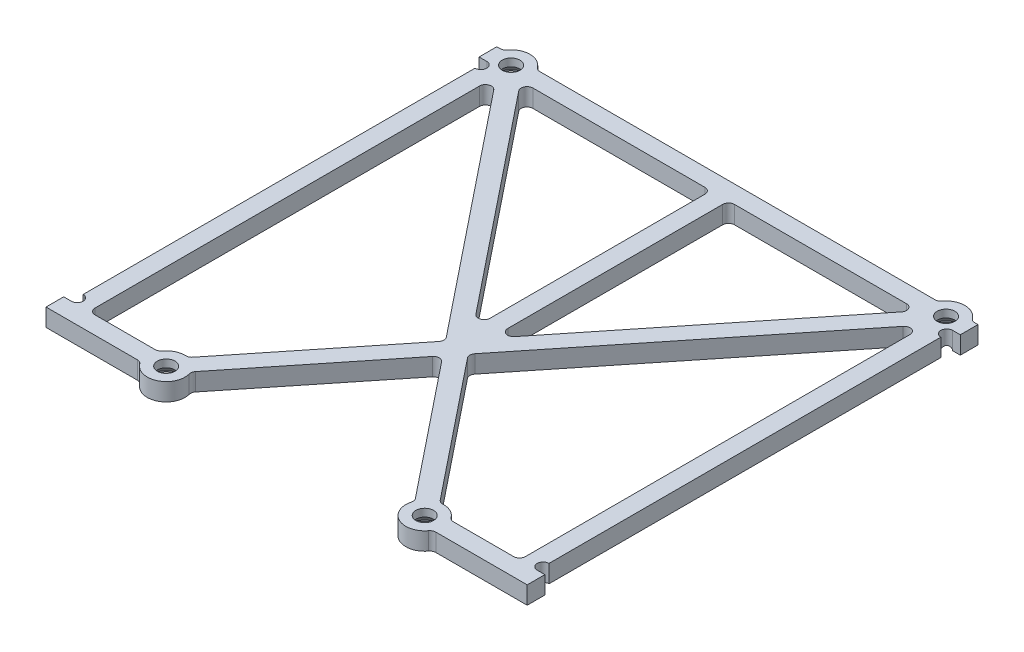
SolidWorks part; units mm, degrees
ref_plane "Front Plane" through (0, 0, 0) normal (0, 0, 1) x (1, 0, 0)
ref_plane "Top Plane" through (0, 0, 0) normal (0, 1, 0) x (1, 0, 0)
ref_plane "Right Plane" through (0, 0, 0) normal (1, 0, 0) x (0, 0, -1)
sketch "Sketch1" plane through (0, 0, 0) normal (0, 1, 0) x (1, 0, 0)
  line L0 (-36.88, 36.725) -> (36.88, 36.725) construction
  line L1 (-39.5, -35.225) -> (-39.5, 35.225)
  line L2 (21.92, -36.725) -> (-21.92, -36.725) construction
  line L3 (-36.5, -35.225) -> (-36.5, 35.225)
  line L4 (0, -40.095) -> (0, -36.725) construction
  line L5 (0, 36.725) -> (0, -36.725) construction
  line L6 (40.8, 38.225) -> (-40.8, 38.225)
  line L9 (40.8, 38.225) -> (40.8, 35.225)
  line L17 (40.8, 35.225) -> (-40.8, 35.225)
  line L18 (-40.8, 38.225) -> (-40.8, 35.225)
  line L23 (40.8, 38.225) -> (-40.8, 35.225) construction
  line L24 (40.8, 35.225) -> (-40.8, 38.225) construction
  line L34 (-40.8, -35.225) -> (40.8, -35.225)
  line L35 (-40.8, -35.225) -> (-40.8, -38.225)
  line L48 (-40.8, -38.225) -> (40.8, -38.225)
  line L54 (40.8, -35.225) -> (40.8, -38.225)
  line L55 (-40.8, -35.225) -> (40.8, -38.225) construction
  line L56 (-40.8, -38.225) -> (40.8, -35.225) construction
  line L60 (-21.92, -36.725) -> (36.88, 36.725) construction
  line L62 (21.92, -36.725) -> (-36.88, 36.725) construction
  line L64 (-1.5, 36.725) -> (-1.5, -36.725)
  line L65 (1.5, 36.725) -> (1.5, -36.725)
  line L66 (23.091, -35.7876) -> (-35.709, 37.6624)
  line L67 (20.749, -37.6624) -> (-38.051, 35.7876)
  line L68 (-20.749, -37.6624) -> (38.051, 35.7876)
  line L69 (-23.091, -35.7876) -> (35.709, 37.6624)
  line L71 (-36.5, 0) -> (-39.5, 0) construction
  line L73 (36.5, -35.225) -> (36.5, 35.225)
  line L74 (39.5, -35.225) -> (39.5, 35.225)
  circle A0 centre (21.92, -36.725) radius 1.5
  circle A1 centre (-21.92, -36.725) radius 1.5
  circle A2 centre (-36.88, 36.725) radius 1.5
  circle A3 centre (36.88, 36.725) radius 1.5
  circle A4 centre (-36.88, 36.725) radius 3.2
  circle A5 centre (-21.92, -36.725) radius 3.2
  circle A6 centre (21.92, -36.725) radius 3.2
  circle A7 centre (36.88, 36.725) radius 3.2
  circle A8 centre (0, -40.095) radius 16
  circle A9 centre (-39.5, 34.225) radius 1
  circle A10 centre (39.5, 34.225) radius 1
  circle A11 centre (-39.5, -34.225) radius 1
  circle A12 centre (39.5, -34.225) radius 1
  circle A13 centre (-35.5, 31.0009) radius 1
  circle A14 centre (35.5, 31.0009) radius 1
  point P10 (0, 0)
  point P58 (-35.2083, 29.9906)
  dimension "D4" = 3
  dimension "D5" = 6.4
  dimension "D6" = 32
  dimension "D11" = 1.5
  dimension "D9" = 3
  dimension "D17" = 2
  dimension "D1" = 74.958
  dimension "D2" = 43.84
  dimension "D3" = 73.76
  dimension "D7" = 3.37
  dimension "D8" = 81.6
  dimension "D10" = 79
  dimension "D12" = 1.5
  dimension "D13" = 1.5
  dimension "D14" = 1.5
  dimension "D15" = 1.5
  dimension "D16" = 1.5
extrude "Shape" add sketch "Sketch1" along normal blind 3 contours L9 | L9 | A4 L1 L34 L3 | A5 L34 L35 L48 | L34 A5 L48 A1 L69 | L69 A5 L34 | L48 A5 | L48 A5 L68 A1 | L68 A5 L34 A1 | L34 A5 L69 | A5 L68 L34 | A5 L34 L68 L64 L67 L69 | L64 L68 L67 | L69 L64 L67 L68 L65 L66 | L69 L67 L64 | L65 L68 L66 | A4 L67 L69 L64 L66 L17 | L64 L69 L66 | L69 L66 L65 | L68 L67 L65 | L66 L69 L65 L17 L64 | A6 L66 L68 L65 L67 L34 | A7 L17 L69 L65 L66 L68 | L48 A6 | L48 A6 L34 L66 A0 | L67 A6 L48 A0 | L34 A6 L67 A0 | A6 L34 L67 | L66 A6 L34 | A0 L66 L34 | L34 A6 L66 | A6 L48 L54 L34 | A1 L34 L69 | A7 L73 L34 L74 | L73 A7 L74 L17 L68 | L68 A7 L73 | L17 A7 L68 L73 | L73 L68 L17 | A3 L17 L68 | L17 A7 L6 A3 L68 | A7 L17 L9 L6 | L69 A7 L17 A3 | A7 L69 L17 | L6 A7 | L6 A7 L69 A3 | A7 L6 A4 L66 L17 L69 | A4 L17 L66 | L67 A4 L17 L3 | L3 A4 L67 | L1 A4 L3 L67 L17 | L67 L3 L17 | A2 L67 L17 | L6 A4 L17 L67 A2 | L17 A4 L66 A2 | L66 A4 L6 A2 | L6 A4 | A4 L6 L18 L17 | A13 L67 A4 L3 | L68 A14 L73 A7 region at (-32.8989, 0, 36.725) region at (-37.9911, 0, 0.5693) region at (-36.0149, 0, -32.4676) region at (-23.02, 0, 34.4354) region at (-24.0408, 0, 36.743) region at (-37.7315, 0, -34.3772) region at (-21.92, 0, 38.9233) region at (-36.4279, 0, -33.6588) region at (-18.2546, 0, -13.4334) region at (-20.8706, 0, 34.6138) region at (-22.5847, 0, 35.3415) region at (-10.7802, 0, 22.7632) region at (-39.0008, 0, -36.743) region at (-40.3721, 0, -36.725) region at (-19.6496, 0, 37.2433) region at (-36.8669, 0, -34.7667) region at (-35.5453, 0, -34.5717) region at (-1.6405, 0, 9.3436) region at (-20.1017, 0, 35.8515) region at (-18.9568, 0, 35.3014) region at (-37.5447, 0, -35.3415) region at (-36.88, 0, -38.9233) region at (-35.0617, 0, -35.8515) region at (-33.9168, 0, -35.3014) region at (-1, 0, 11.7438) region at (0, 0, 9.3436) region at (-1, 0, 6.9435) region at (-34.6096, 0, -37.2433) region at (0, 0, -36.7255) region at (1, 0, 11.7438) region at (0, 0, -14.6057) region at (1, 0, 6.9435) region at (36.88, 0, -38.9233) region at (34.6096, 0, -37.2433) region at (19.6496, 0, 37.2433) region at (21.92, 0, 38.9233) region at (10.7802, 0, 22.7632) region at (1.6405, 0, 9.3436) region at (18.2546, 0, -13.4334) region at (39.0008, 0, -36.743) region at (40.3721, 0, -36.725) region at (33.9168, 0, -35.3014) region at (35.0617, 0, -35.8515) region at (24.0408, 0, 36.743) region at (20.1017, 0, 35.8515) region at (18.9568, 0, 35.3014) region at (32.8989, 0, 36.725) region at (35.5453, 0, -34.5717) region at (20.8706, 0, 34.6138) region at (23.02, 0, 34.4354) region at (36.0149, 0, -32.4676) region at (37.5447, 0, -35.3415) region at (36.8669, 0, -34.7667) region at (36.4279, 0, -33.6588) region at (22.5847, 0, 35.3415) region at (37.9911, 0, 0.5693) region at (37.7315, 0, -34.3772)
fillet "Mill fillets" radius 1 23 edges at (39.7067, 1.5, -38.225) (34.0533, 1.5, -38.225) (-39.7067, 1.5, -38.225) (-34.0533, 1.5, -38.225) (-18.9825, 1.5, 35.4558) (-24.7467, 1.5, 38.225) (24.7467, 1.5, 38.225) (18.9825, 1.5, 35.4558) (24.7467, 1.5, 35.225) (21.3245, 1.5, 33.5809) (1.9214, 1.5, 9.3436) (-21.3245, 1.5, 33.5809) (-24.7467, 1.5, 35.225) (-1.9214, 1.5, 9.3436) (-36.5, 1.5, 35.225) (36.5, 1.5, 35.225) (-1.5, 1.5, 5.0697) (1.5, 1.5, 5.0697) (33.7577, 1.5, -35.225) (1.5, 1.5, -35.225) (-1.5, 1.5, -35.225) (-33.7577, 1.5, -35.225) (0, 1.5, 11.7438)
hole_wizard "M3 countersunks" positions "Sketch2" profile "Sketch3" countersink size "M3" standard "ANSI Metric" end condition through all
sketch "Sketch2" plane through (0, 0, 0) normal (0, -1, 0) x (-1, 0, 0)
  point P0 (21.92, -36.725)
  point P3 (-21.92, -36.725)
  point P6 (-36.88, 36.725)
  point P9 (36.88, 36.725)
sketch "Sketch3" plane through (-21.92, 0, 36.725) normal (1, 0, 0) x (0, 0, -1)
  line L0 (0, 0) -> (0, 3)
  line L1 (0, 3) -> (1.5, 3)
  line L2 (1.5, 3) -> (1.5, 1.7)
  line L3 (1.5, 1.7) -> (3, 0.2)
  line L4 (3, 0.2) -> (3, 0)
  line L6 (3, 0) -> (0, 0)
  line L7 (-1.5, 1.7) -> (-3, 0.2) construction
  line L11 (0, -6.35) -> (0, 107.95) construction
  dimension "Thru Hole Dia." = 3
  dimension "Thru Hole Depth" = 3
  dimension "C'Sink Dia." = 6
  dimension "C'Sink Angle" = 90
  dimension "Head Clearance" = 0.2
